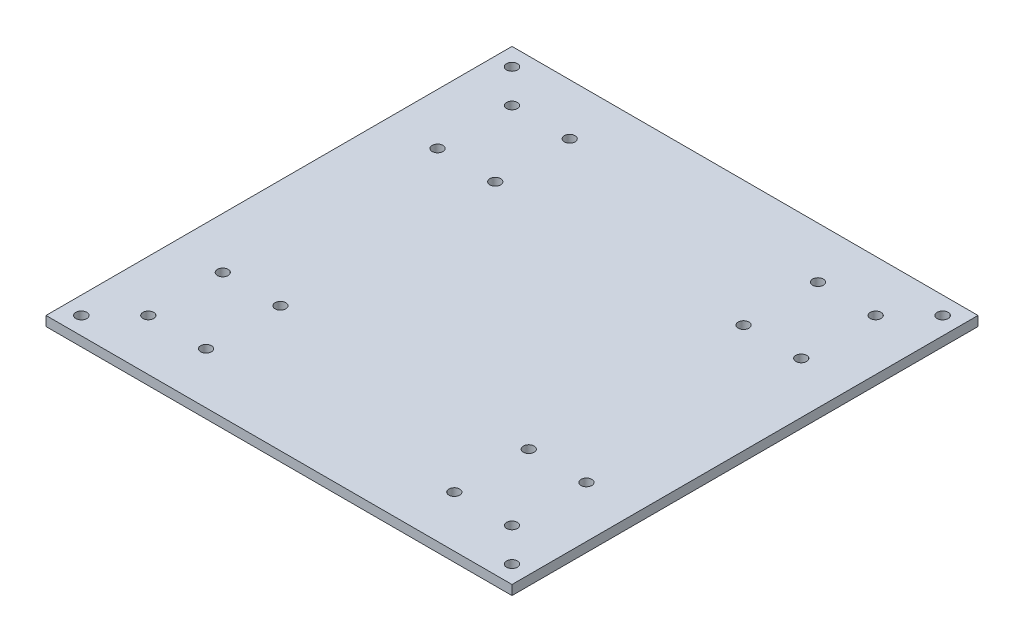
SolidWorks part; units mm, degrees
ref_plane "Front Plane" through (0, 0, 0) normal (0, 0, 1) x (1, 0, 0)
ref_plane "Top Plane" through (0, 0, 0) normal (0, 1, 0) x (1, 0, 0)
ref_plane "Right Plane" through (0, 0, 0) normal (1, 0, 0) x (0, 0, -1)
sketch "Sketch1" plane through (0, 0, 0) normal (0, 1, 0) x (1, 0, 0)
  line L1 (0, 0) -> (145, 0)
  line L2 (0, 0) -> (0, 145)
  line L3 (0, 145) -> (145, 145)
  line L4 (145, 0) -> (145, 145)
  dimension "D1" = 145
extrude "Boss-Extrude1" add sketch "Sketch1" along normal blind 3
sketch "Sketch2" plane through (0, 3, 0) normal (0, 1, 0) x (1, 0, 0)
  line L0 (0, 72.5) -> (145, 72.5) construction
  line L1 (0, 145) -> (0, 0) construction
  line L2 (145, 0) -> (145, 145) construction
  line L3 (72.5, 145) -> (72.5, 0) construction
  line L4 (145, 145) -> (0, 145) construction
  line L5 (0, 0) -> (145, 0) construction
  circle A0 centre (5.5, 5.5) radius 1.705
  circle A1 centre (139.5, 5.5) radius 1.705
  circle A2 centre (5.5, 139.5) radius 1.705
  circle A3 centre (139.5, 139.5) radius 1.705
  dimension "D3" = 3.41
  dimension "D1" = 5.5
  dimension "D2" = 5.5
extrude "Cut-Extrude1" cut sketch "Sketch2" against normal through all
sketch "Sketch3" plane through (0, 3, 0) normal (0, 1, 0) x (1, 0, 0)
  line L0 (0, 0) -> (145, 0) construction
  line L1 (0, 145) -> (0, 0) construction
  line L2 (0, 72.5) -> (145, 72.5) construction
  line L3 (145, 0) -> (145, 145) construction
  line L4 (72.5, 0) -> (72.5, 145) construction
  line L5 (145, 145) -> (0, 145) construction
  circle A0 centre (15.92, 15.92) radius 1.675
  circle A1 centre (33.87, 15.92) radius 1.675
  circle A2 centre (15.92, 39.08) radius 1.675
  circle A3 centre (33.87, 39.08) radius 1.675
  circle A4 centre (33.87, 105.92) radius 1.675
  circle A5 centre (15.92, 105.92) radius 1.675
  circle A6 centre (33.87, 129.08) radius 1.675
  circle A7 centre (15.92, 129.08) radius 1.675
  circle A8 centre (111.13, 39.08) radius 1.675
  circle A9 centre (129.08, 39.08) radius 1.675
  circle A10 centre (111.13, 15.92) radius 1.675
  circle A11 centre (129.08, 15.92) radius 1.675
  circle A12 centre (129.08, 129.08) radius 1.675
  circle A13 centre (111.13, 129.08) radius 1.675
  circle A14 centre (129.08, 105.92) radius 1.675
  circle A15 centre (111.13, 105.92) radius 1.675
  dimension "D5" = 3.35
  dimension "D1" = 15.92
  dimension "D2" = 15.92
  dimension "D3" = 17.95
  dimension "D4" = 23.16
extrude "Cut-Extrude2" cut sketch "Sketch3" against normal through all
